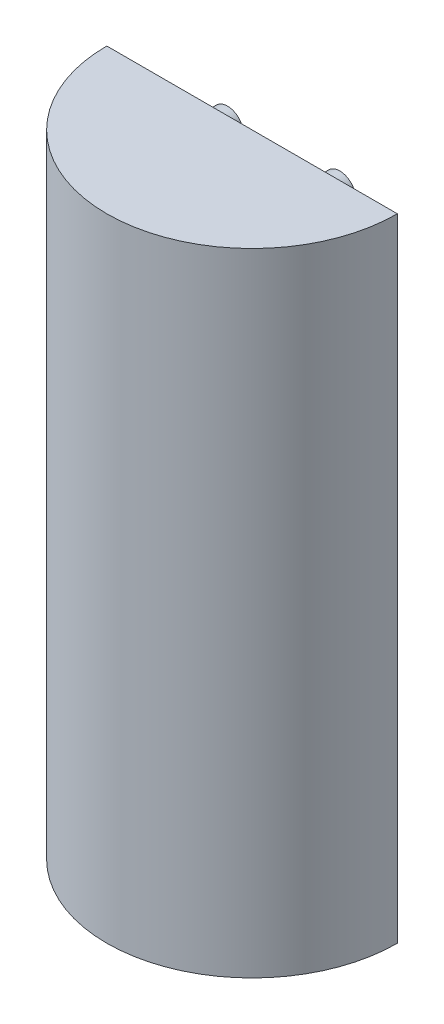
SolidWorks part; units mm, degrees
material "ABS"
ref_plane "Спереди" through (0, 0, 0) normal (0, 0, 1) x (1, 0, 0)
ref_plane "Сверху" through (0, 0, 0) normal (0, 1, 0) x (1, 0, 0)
ref_plane "Справа" through (0, 0, 0) normal (1, 0, 0) x (0, 0, -1)
sketch "Эскиз1" plane through (0, 0, 0) normal (0, 1, 0) x (1, 0, 0)
  line L0 (-23, 0) -> (23, 0)
  arc A0 (-23, 0) -> (23, 0) centre (0, 0) ccw
  dimension "D1" = 23
extrude "Бобышка-Вытянуть1" add sketch "Эскиз1" along normal blind 100
sketch "Эскиз2" plane through (0, 0, 0) normal (0, 0, -1) x (-1, 0, 0)
  line L0 (0, 100) -> (0, 0) construction
  line L1 (-23, 100) -> (23, 100) construction
  line L2 (-23, 50) -> (5.22, 50) construction
  line L3 (-23, 100) -> (-23, 0) construction
  line L4 (-8.89, 93.815) -> (8.89, 93.815) construction
  line L5 (-8.89, 93.815) -> (-8.89, 6.185) construction
  circle A0 centre (-8.89, 93.815) radius 2.5
  circle A1 centre (8.89, 93.815) radius 2.5
  circle A2 centre (-8.89, 6.185) radius 2.5
  circle A3 centre (8.89, 6.185) radius 2.5
  point P17 (0, 93.815)
  point P19 (-8.89, 50)
  dimension "D1" = 5
  dimension "D2" = 2
  dimension "D3" = 2
extrude "Бобышка-Вытянуть2" add sketch "Эскиз2" along normal blind 5
